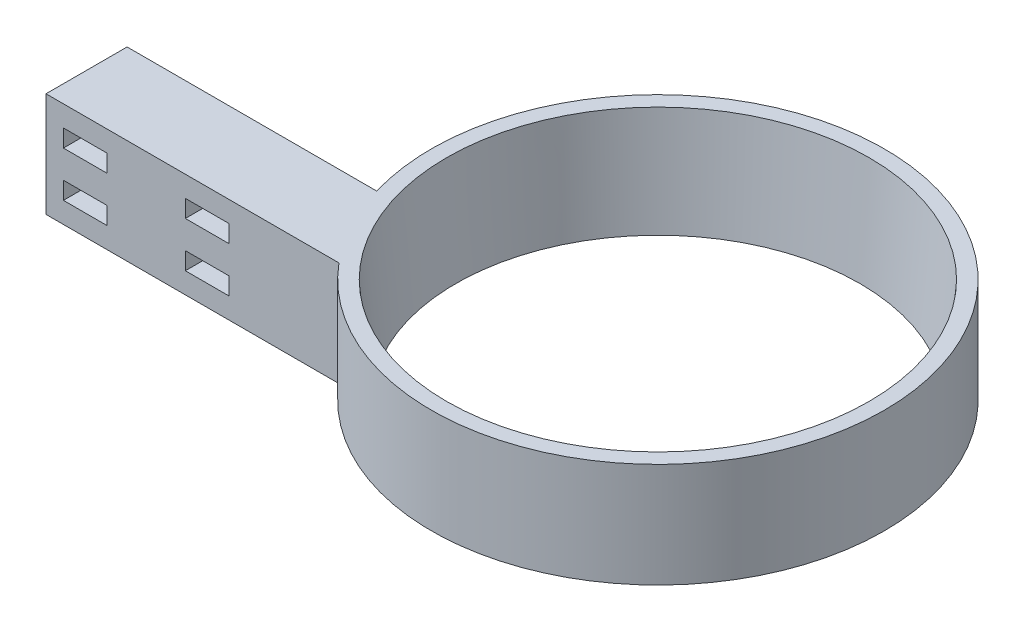
SolidWorks part; units mm, degrees
ref_plane "Front Plane" through (0, 0, 0) normal (0, 0, 1) x (1, 0, 0)
ref_plane "Top Plane" through (0, 0, 0) normal (0, 1, 0) x (1, 0, 0)
ref_plane "Right Plane" through (0, 0, 0) normal (1, 0, 0) x (0, 0, -1)
sketch "Sketch1" plane through (0, 0, 0) normal (0, 1, 0) x (1, 0, 0)
  line L0 (0, 0) -> (-41.275, 0) construction
  circle A0 centre (0, 0) radius 41.275
  dimension "D1" = 82.55
extrude "Outer Circle" add sketch "Sketch1" along normal blind 19.05 contours A0
ref_plane "Connector Midplane" through (0, 0, 19.05) normal (0, 0, 1) x (1, 0, 0)
sketch "Sketch3" plane through (0, 0, 0) normal (0, -1, 0) x (1, 0, 0)
  line L0 (0, 0) -> (-41.275, 0) construction
  line L1 (-31.6935, 26.4414) -> (-85.09, 26.4414)
  line L2 (-85.09, 26.4414) -> (-85.09, 11.6586)
  line L3 (-85.09, 11.6586) -> (-39.5942, 11.6586)
  line L4 (10.4775, 19.05) -> (-10.4775, 19.05) construction
  circle A0 centre (0, 0) radius 41.275 construction
  arc A1 (-39.5942, 11.6586) -> (-31.6935, 26.4414) centre (0, 0) cw
  point P7 (-85.09, 19.05)
  dimension "D1" = 14.7828
  dimension "D2" = 43.815
extrude "Connector" add sketch "Sketch3" against normal blind 3.175 contours L3 A1 L1 L2
sketch "Sketch4" plane through (0, 0, 26.4414) normal (0, 0, 1) x (1, 0, 0)
  line L0 (-85.09, 3.175) -> (-85.09, 19.05)
  line L1 (-85.09, 19.05) -> (-31.6935, 19.05)
  line L2 (41.275, 19.05) -> (-41.275, 19.05) construction
  line L3 (-31.6935, 19.05) -> (-31.6935, 3.175)
  line L4 (-31.6935, 3.175) -> (-85.09, 3.175) construction
  line L5 (-31.6935, 3.175) -> (-85.09, 3.175)
  line L6 (-31.6935, 3.175) -> (-39.5942, 3.175) construction
  line L7 (-31.6935, 3.175) -> (-31.6935, 0) construction
sketch "Sketch5" plane through (0, 0, 11.6586) normal (0, 0, -1) x (-1, 0, 0)
  line L0 (85.09, 3.175) -> (85.09, 19.05)
  line L1 (85.09, 19.05) -> (31.6935, 19.05)
  line L2 (31.6935, 19.05) -> (31.6935, 3.175)
  line L3 (31.6935, 3.175) -> (85.09, 3.175)
  line L4 (41.275, 19.05) -> (-41.275, 19.05) construction
extrude "Outside Wall" add sketch "Sketch4" against normal blind 3.175
extrude "Inside Wall" add sketch "Sketch5" against normal up to surface (11.6078 mm away) up to face at (-59.5913, 11.1125, 23.2664)
sketch "Sketch2" plane through (0, 0, 0) normal (0, -1, 0) x (1, 0, 0)
  circle A0 centre (0, 0) radius 36.83
  dimension "D1" = 73.66
extrude "Cup Cut" cut sketch "Sketch2" against normal through all draft 5 draft outward yes
sketch "Sketch7" plane through (0, 0, 26.4414) normal (0, 0, 1) x (1, 0, 0)
  line L0 (-85.09, 9.525) -> (-31.6935, 9.525) construction
  line L1 (-85.09, 19.05) -> (-85.09, 0) construction
  line L2 (-31.6935, 19.05) -> (-31.6935, 0) construction
  line L4 (-31.6935, 19.05) -> (-85.09, 19.05) construction
  line L7 (-81.915, 15.24) -> (-73.9775, 15.24)
  line L8 (-81.915, 15.24) -> (-81.915, 12.065)
  line L9 (-81.915, 12.065) -> (-73.9775, 12.065)
  line L10 (-73.9775, 15.24) -> (-73.9775, 12.065)
  line L11 (-81.915, 15.24) -> (-73.9775, 12.065) construction
  line L12 (-81.915, 12.065) -> (-73.9775, 15.24) construction
  point P12 (-77.9462, 13.6525)
  dimension "D1" = 3.175
  dimension "D2" = 7.9375
  dimension "D3" = 9.525
  dimension "D4" = 3.81
  dimension "D5" = 3.175
extrude "Slot" cut sketch "Sketch7" against normal up to next
ref_plane "Plane2" through (0, 9.525, 0) normal (0, 1, 0) x (1, 0, 0)
pattern_linear "LPattern1" count 2 spacing 22.225 along (1, 0, 0) of "Slot"
mirror "Mirror2" about plane through (0, 9.525, 0) normal (0, 1, 0) of "LPattern1"
sketch "Sketch8" plane through (0, 0, 26.4414) normal (0, 0, 1) x (1, 0, 0)
  line L0 (-85.09, 9.525) -> (-50.3371, 9.525) construction
  line L1 (-85.09, 19.05) -> (-85.09, 0) construction
  line L2 (-81.915, 15.24) -> (-73.9775, 12.065) construction
  line L3 (-73.9775, 15.24) -> (-81.915, 15.24) construction
  line L4 (-81.915, 15.24) -> (-81.915, 12.065) construction
  line L5 (-73.9775, 15.24) -> (-81.915, 12.065) construction
  point P16 (-77.9462, 13.6525)
  dimension "D1" = 4.1275
  dimension "D2" = 7.1438
sketch "Sketch6" plane through (0, 19.05, 0) normal (0, 1, 0) x (1, 0, 0)
  line L0 (-85.09, -11.6586) -> (-85.09, -26.4414) construction
  line L1 (-85.09, -20.5486) -> (-78.74, -20.5486)
  line L2 (-85.09, -20.5486) -> (-85.09, -17.5514)
  line L3 (-85.09, -17.5514) -> (-78.74, -17.5514)
  line L4 (-78.74, -20.5486) -> (-78.74, -17.5514)
  line L5 (-72.39, -20.5486) -> (-72.39, -17.5514)
  line L6 (-72.39, -20.5486) -> (-66.04, -20.5486)
  line L7 (-66.04, -20.5486) -> (-66.04, -17.5514)
  line L8 (-72.39, -17.5514) -> (-66.04, -17.5514)
  line L9 (-59.69, -20.5486) -> (-59.69, -17.5514)
  line L10 (-59.69, -20.5486) -> (-53.34, -20.5486)
  line L11 (-53.34, -20.5486) -> (-53.34, -17.5514)
  line L12 (-59.69, -17.5514) -> (-53.34, -17.5514)
  line L13 (-10.4775, -19.05) -> (10.4775, -19.05) construction
  line L14 (-59.69, -17.5514) -> (-53.34, -17.5514)
  line L15 (-53.34, -17.5514) -> (-53.34, -20.5486)
  line L16 (-59.69, -20.5486) -> (-53.34, -20.5486)
  line L17 (-59.69, -17.5514) -> (-59.69, -20.5486)
  line L18 (-72.39, -17.5514) -> (-66.04, -17.5514)
  line L19 (-66.04, -17.5514) -> (-66.04, -20.5486)
  line L20 (-72.39, -20.5486) -> (-66.04, -20.5486)
  line L21 (-72.39, -17.5514) -> (-72.39, -20.5486)
  line L22 (-85.09, -20.5486) -> (-78.74, -20.5486)
  line L23 (-78.74, -17.5514) -> (-78.74, -20.5486)
  line L24 (-85.09, -17.5514) -> (-78.74, -17.5514)
  line L25 (-85.09, -17.5514) -> (-85.09, -20.5486)
  point P6 (-85.09, -19.05)
  point P7 (-85.09, -19.05)
  dimension "D1" = 2.9972
  dimension "D2" = 6.35
  dimension "D3" = 3
  dimension "D4" = 6.35
extrude "Boss-Extrude5" [suppressed] add sketch "Sketch6" along normal blind 3.429
fillet "Fillet1" [suppressed] radius 0.508
mirror "Mirror1" [suppressed] about plane through (0, 9.525, 0) normal (0, 1, 0)
ref_plane "Plane3" through (0, 0, -50.8) normal (0, 0, 1) x (1, 0, 0)
